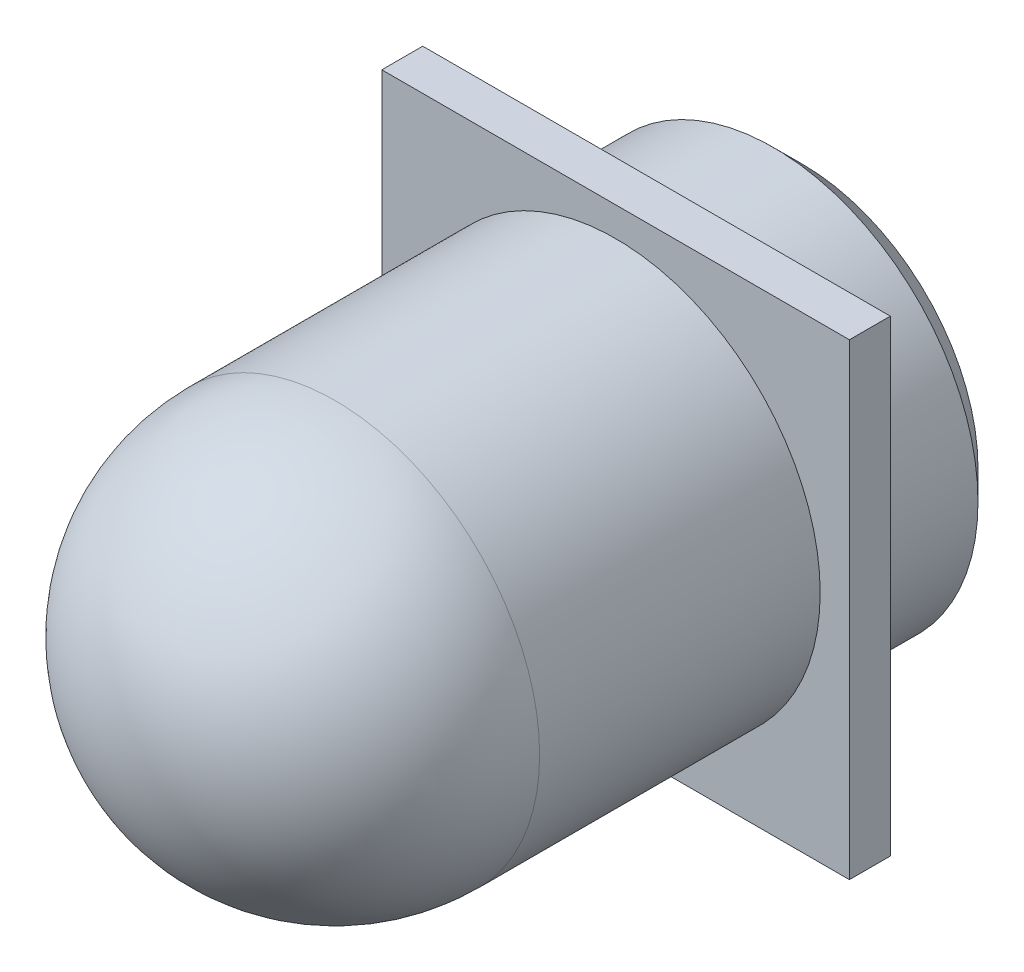
SolidWorks part; units mm, degrees
ref_plane "Front Plane" through (0, 0, 0) normal (0, 0, 1) x (1, 0, 0)
ref_plane "Top Plane" through (0, 0, 0) normal (0, 1, 0) x (1, 0, 0)
ref_plane "Right Plane" through (0, 0, 0) normal (1, 0, 0) x (0, 0, -1)
sketch "Sketch1" plane through (0, 0, 0) normal (0, 0, 1) x (1, 0, 0)
  circle A0 centre (0, 0) radius 3.5
  dimension "D1" = 7
extrude "Boss-Extrude1" add sketch "Sketch1" along normal blind 11.5
fillet "Fillet1" radius 3.5 1 edges at (3.5, 0, 11.5)
ref_plane "Plane1" through (0, 0, 2) normal (0, 0, -1) x (-1, 0, 0)
sketch "Sketch3" plane through (0, 0, 2) normal (0, 0, -1) x (-1, 0, 0)
  line L1 (4, -4) -> (-4, -4)
  line L2 (4, -4) -> (4, 4)
  line L3 (4, 4) -> (-4, 4)
  line L4 (-4, -4) -> (-4, 4)
  line L5 (4, -4) -> (-4, 4) construction
  line L6 (4, 4) -> (-4, -4) construction
  point P0 (0, 0)
  dimension "D1" = 8
  dimension "D2" = 8
extrude "Boss-Extrude2" add sketch "Sketch3" against normal blind 1.2
chamfer "Chamfer1" distance 0.5 angle 45 1 edges at (3.5, 0, 0)
chamfer "Chamfer2" distance 0.5 angle 45 4 edges at (0, -4, 2) (-4, 0, 2) (4, 0, 2) (0, 4, 2)
